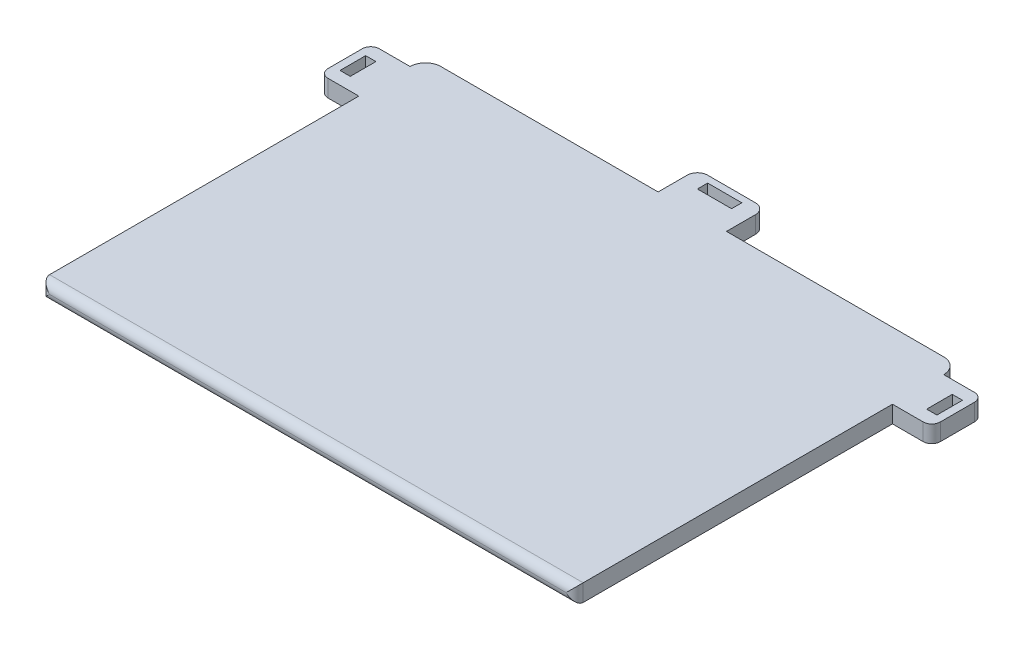
SolidWorks part; units mm, degrees
ref_plane "Front Plane" through (0, 0, 0) normal (0, 0, 1) x (1, 0, 0)
ref_plane "Top Plane" through (0, 0, 0) normal (0, 1, 0) x (1, 0, 0)
ref_plane "Right Plane" through (0, 0, 0) normal (1, 0, 0) x (0, 0, -1)
sketch "Sketch1" plane through (0, 0, 0) normal (0, 1, 0) x (1, 0, 0)
  line L1 (-396.621, -285.75) -> (396.621, -285.75)
  line L2 (-396.621, -285.75) -> (-396.621, 285.75)
  line L3 (-396.621, 285.75) -> (396.621, 285.75)
  line L4 (396.621, -285.75) -> (396.621, 285.75)
  line L5 (-396.621, -285.75) -> (396.621, 285.75) construction
  line L6 (-396.621, 285.75) -> (396.621, -285.75) construction
  point P0 (0, 0)
  dimension "D1" = 793.242
  dimension "D2" = 571.5
extrude "Boss-Extrude1" add sketch "Sketch1" along normal blind 25.4
fillet "Fillet1" radius 17.78 5 edges at (0, 25.4, 285.75) (396.621, 12.7, 285.75) (396.621, 12.7, -285.75) (-396.621, 12.7, -285.75) (-396.621, 12.7, 285.75)
sketch "Sketch2" plane through (-396.621, 0, 0) normal (-1, 0, 0) x (0, 0, 1)
  line L0 (-267.97, 25.4) -> (267.97, 25.4) construction
  line L1 (-262.89, 25.4) -> (-186.69, 25.4)
  line L2 (-262.89, 25.4) -> (-262.89, 0)
  line L3 (-262.89, 0) -> (-186.69, 0)
  line L4 (-186.69, 25.4) -> (-186.69, 0)
  line L5 (-267.97, 0) -> (267.97, 0) construction
  line L6 (-285.75, 0) -> (-285.75, 25.4) construction
  dimension "D1" = 22.86
  dimension "D2" = 76.2
extrude "Boss-Extrude2" add sketch "Sketch2" along normal blind 58.42
fillet "Fillet2" radius 12.7 2 edges at (-455.041, 12.7, -186.69) (-455.041, 12.7, -262.89)
sketch "Sketch3" plane through (0, 25.4, 0) normal (0, 1, 0) x (1, 0, 0)
  line L0 (-442.341, 186.69) -> (-396.621, 186.69) construction
  line L1 (-396.621, 262.89) -> (-422.021, 262.89)
  line L2 (-396.621, 262.89) -> (-396.621, 186.69)
  line L3 (-396.621, 186.69) -> (-422.021, 186.69)
  line L4 (-422.021, 262.89) -> (-422.021, 186.69)
  line L5 (-442.341, 262.89) -> (-396.621, 262.89) construction
  line L6 (-422.021, 262.89) -> (-447.421, 262.89)
  line L7 (-422.021, 262.89) -> (-422.021, 186.69)
  line L8 (-422.021, 186.69) -> (-447.421, 186.69)
  line L9 (-447.421, 262.89) -> (-447.421, 186.69)
  line L13 (-443.611, 243.84) -> (-428.371, 243.84)
  line L14 (-443.611, 243.84) -> (-443.611, 205.74)
  line L15 (-443.611, 205.74) -> (-428.371, 205.74)
  line L16 (-428.371, 243.84) -> (-428.371, 205.74)
  point P13 (-429.641, 224.79)
  point P18 (-443.611, 224.79)
  dimension "D1" = 25.4
  dimension "D2" = 25.4
  dimension "D3" = 0
  dimension "D4" = 38.1
  dimension "D5" = 15.24
  dimension "D6" = 6.35
  dimension "D7" = 38.1
extrude "Cut-Extrude1" cut sketch "Sketch3" against normal through all contours L14 L13 L16 L15
ref_plane "Plane1" through (0, 0, 0) normal (1, 0, 0) x (0, 0, -1)
mirror "Mirror2" about plane through (0, 0, 0) normal (1, 0, 0) of "Boss-Extrude1", "Fillet2", "Cut-Extrude1", "Boss-Extrude2"
sketch "Sketch4" plane through (0, 0, 0) normal (1, 0, 0) x (0, 0, -1)
  line L1 (285.75, 0) -> (344.17, 0)
  line L2 (285.75, 0) -> (285.75, 25.4)
  line L3 (285.75, 25.4) -> (344.17, 25.4)
  line L4 (344.17, 0) -> (344.17, 25.4)
  dimension "D1" = 58.42
extrude "Boss-Extrude3" add sketch "Sketch4" along normal mid plane 101.6
fillet "Fillet3" radius 22.86 1 edges at (396.621, 12.7, -285.75)
fillet "Fillet4" radius 22.86 1 edges at (-396.621, 12.7, -285.75)
sketch "Sketch5" plane through (0, 25.4, 0) normal (0, 1, 0) x (1, 0, 0)
  line L0 (-50.8, 285.75) -> (-373.761, 285.75) construction
  line L3 (25.4, 334.01) -> (-25.4, 334.01)
  line L13 (25.4, 334.01) -> (25.4, 318.77)
  line L14 (25.4, 318.77) -> (-25.4, 318.77)
  line L15 (-25.4, 334.01) -> (-25.4, 318.77)
  point P5 (0, 334.01)
  dimension "D1" = 33.02
  dimension "D2" = 50.8
  dimension "D3" = 15.24
sketch "Sketch6" plane through (0, 25.4, 0) normal (0, 1, 0) x (1, 0, 0)
extrude "Cut-Extrude2" cut sketch "Sketch5" against normal through all
fillet "Fillet7" radius 15.24 2 edges at (50.8, 12.7, -344.17) (-50.8, 12.7, -344.17)
fillet "Fillet8" radius 12.7 4 edges at (396.621, 12.7, 285.75) (-396.621, 12.7, 285.75) (0, 0, 285.75) (0, 25.4, 285.75)
